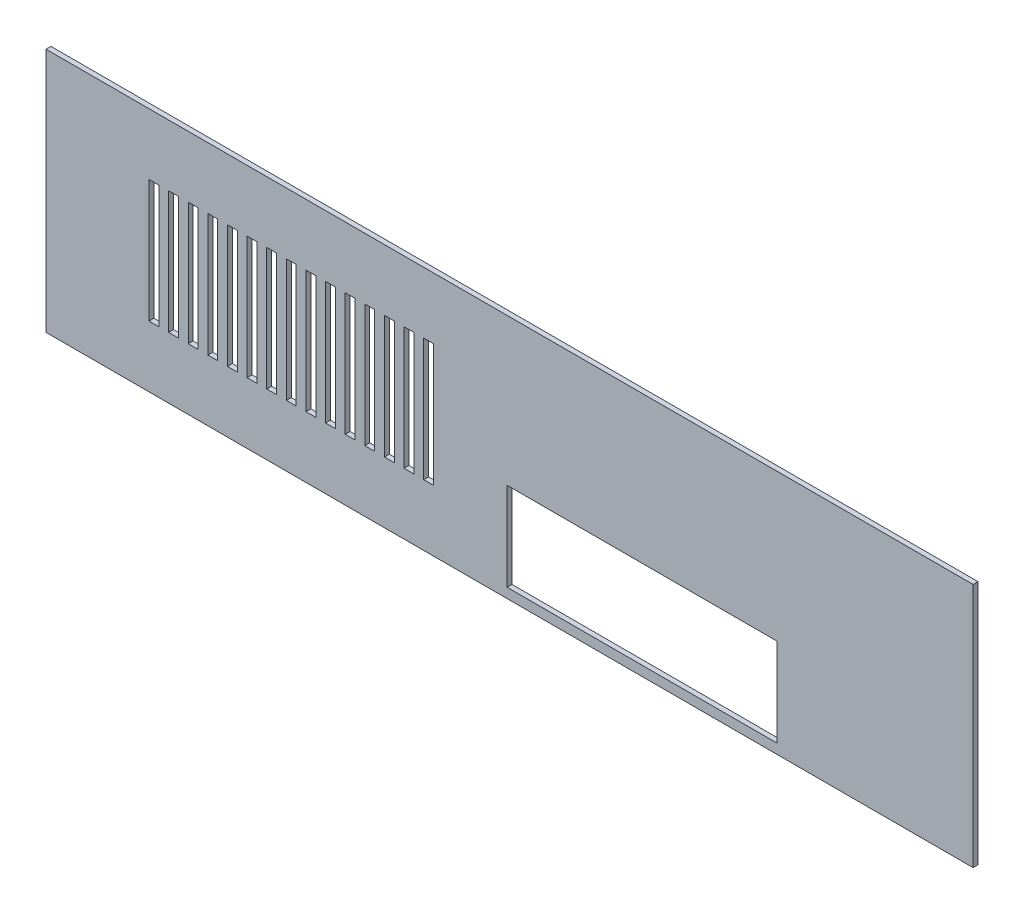
SolidWorks part; units mm, degrees
ref_plane "Front Plane" through (0, 0, 0) normal (0, 0, 1) x (1, 0, 0)
ref_plane "Top Plane" through (0, 0, 0) normal (0, 1, 0) x (1, 0, 0)
ref_plane "Right Plane" through (0, 0, 0) normal (1, 0, 0) x (0, 0, -1)
sketch "Sketch1" plane through (0, 0, 0) normal (0, 0, 1) x (1, 0, 0)
  line L1 (-61.6344, 41.198) -> (127.3656, 41.198)
  line L2 (-61.6344, 41.198) -> (-61.6344, -8.802)
  line L3 (-61.6344, -8.802) -> (127.3656, -8.802)
  line L4 (127.3656, 41.198) -> (127.3656, -8.802)
  dimension "D1" = 50
  dimension "D2" = 189
extrude "Boss-Extrude1" add sketch "Sketch1" along normal blind 1
sketch "Sketch2" plane through (0, 0, 1) normal (0, 0, 1) x (1, 0, 0)
  line L0 (-61.6344, -8.802) -> (127.3656, -8.802) construction
  line L1 (32.3656, 11.198) -> (87.3656, 11.198)
  line L2 (32.3656, 11.198) -> (32.3656, -6.802)
  line L3 (32.3656, -6.802) -> (87.3656, -6.802)
  line L4 (87.3656, 11.198) -> (87.3656, -6.802)
  line L5 (127.3656, -8.802) -> (127.3656, 41.198) construction
  dimension "D1" = 55
  dimension "D2" = 18
  dimension "D3" = 2
  dimension "D4" = 40
extrude "Cut-Extrude1" cut sketch "Sketch2" against normal through all
sketch "Sketch3" plane through (0, 0, 0) normal (0, 0, -1) x (-1, 0, 0)
  line L0 (-13.3656, 28.698) -> (-11.3656, 28.698)
  line L1 (-17.3656, 28.698) -> (-15.3656, 28.698)
  line L2 (-17.3656, 28.698) -> (-17.3656, 3.698)
  line L3 (-17.3656, 3.698) -> (-15.3656, 3.698)
  line L4 (-15.3656, 28.698) -> (-15.3656, 3.698)
  line L5 (-32.3656, 11.198) -> (-32.3656, -6.802) construction
  line L6 (-13.3656, 28.698) -> (-13.3656, 3.698)
  line L7 (-127.3656, 41.198) -> (61.6344, 41.198) construction
  line L8 (-13.3656, 3.698) -> (-11.3656, 3.698)
  line L9 (-11.3656, 28.698) -> (-11.3656, 3.698)
  line L10 (-9.3656, 28.698) -> (-7.3656, 28.698)
  line L11 (-9.3656, 28.698) -> (-9.3656, 3.698)
  line L12 (-9.3656, 3.698) -> (-7.3656, 3.698)
  line L13 (-7.3656, 28.698) -> (-7.3656, 3.698)
  line L14 (-5.3656, 28.698) -> (-3.3656, 28.698)
  line L15 (-5.3656, 28.698) -> (-5.3656, 3.698)
  line L16 (-5.3656, 3.698) -> (-3.3656, 3.698)
  line L17 (-3.3656, 28.698) -> (-3.3656, 3.698)
  line L18 (-1.3656, 28.698) -> (0.6344, 28.698)
  line L19 (-1.3656, 28.698) -> (-1.3656, 3.698)
  line L20 (-1.3656, 3.698) -> (0.6344, 3.698)
  line L21 (0.6344, 28.698) -> (0.6344, 3.698)
  line L22 (2.6344, 28.698) -> (4.6344, 28.698)
  line L23 (2.6344, 28.698) -> (2.6344, 3.698)
  line L24 (2.6344, 3.698) -> (4.6344, 3.698)
  line L25 (4.6344, 28.698) -> (4.6344, 3.698)
  line L26 (6.6344, 28.698) -> (8.6344, 28.698)
  line L27 (6.6344, 28.698) -> (6.6344, 3.698)
  line L28 (6.6344, 3.698) -> (8.6344, 3.698)
  line L29 (8.6344, 28.698) -> (8.6344, 3.698)
  line L30 (10.6344, 28.698) -> (12.6344, 28.698)
  line L31 (10.6344, 28.698) -> (10.6344, 3.698)
  line L32 (10.6344, 3.698) -> (12.6344, 3.698)
  line L33 (12.6344, 28.698) -> (12.6344, 3.698)
  line L34 (14.6344, 28.698) -> (16.6344, 28.698)
  line L35 (14.6344, 28.698) -> (14.6344, 3.698)
  line L36 (14.6344, 3.698) -> (16.6344, 3.698)
  line L37 (16.6344, 28.698) -> (16.6344, 3.698)
  line L38 (18.6344, 28.698) -> (20.6344, 28.698)
  line L39 (18.6344, 28.698) -> (18.6344, 3.698)
  line L40 (18.6344, 3.698) -> (20.6344, 3.698)
  line L41 (20.6344, 28.698) -> (20.6344, 3.698)
  line L42 (22.6344, 28.698) -> (24.6344, 28.698)
  line L43 (22.6344, 28.698) -> (22.6344, 3.698)
  line L44 (22.6344, 3.698) -> (24.6344, 3.698)
  line L45 (24.6344, 28.698) -> (24.6344, 3.698)
  line L46 (26.6344, 28.698) -> (28.6344, 28.698)
  line L47 (26.6344, 28.698) -> (26.6344, 3.698)
  line L48 (26.6344, 3.698) -> (28.6344, 3.698)
  line L49 (28.6344, 28.698) -> (28.6344, 3.698)
  line L50 (30.6344, 28.698) -> (32.6344, 28.698)
  line L51 (30.6344, 28.698) -> (30.6344, 3.698)
  line L52 (30.6344, 3.698) -> (32.6344, 3.698)
  line L53 (32.6344, 28.698) -> (32.6344, 3.698)
  line L54 (34.6344, 28.698) -> (36.6344, 28.698)
  line L55 (34.6344, 28.698) -> (34.6344, 3.698)
  line L56 (34.6344, 3.698) -> (36.6344, 3.698)
  line L57 (36.6344, 28.698) -> (36.6344, 3.698)
  line L58 (38.6344, 28.698) -> (40.6344, 28.698)
  line L59 (38.6344, 28.698) -> (38.6344, 3.698)
  line L60 (38.6344, 3.698) -> (40.6344, 3.698)
  line L61 (40.6344, 28.698) -> (40.6344, 3.698)
  dimension "D1" = 2
  dimension "D2" = 25
  dimension "D3" = 15
  dimension "D5" = 12.5
extrude "Cut-Extrude2" cut sketch "Sketch3" against normal through all
